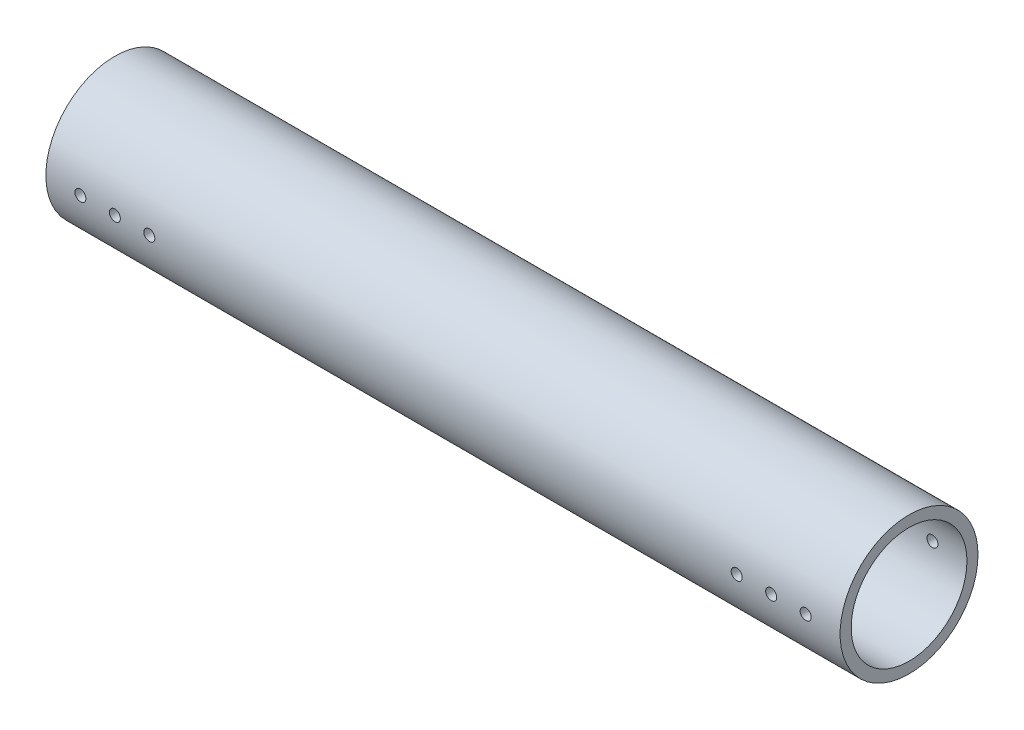
SolidWorks part; units mm, degrees
material "Zoltek Panex 33"
ref_plane "Спереди" through (0, 0, 0) normal (0, 0, 1) x (1, 0, 0)
ref_plane "Сверху" through (0, 0, 0) normal (0, 1, 0) x (1, 0, 0)
ref_plane "Справа" through (0, 0, 0) normal (1, 0, 0) x (0, 0, -1)
other "Configuration Table"
sketch "Эскиз2" plane through (0, 0, 0) normal (1, 0, 0) x (0, 0, -1)
  circle A0 centre (0, 0) radius 25
  circle A1 centre (0, 0) radius 21
  dimension "D1" = 50
  dimension "D2" = 42
extrude "Бобышка-Вытянуть2" add sketch "Эскиз2" along normal blind 288
ref_plane "Плоскость1" through (0, 0, 25) normal (0, 0, 1) x (1, 0, 0)
sketch "Эскиз4" plane through (0, 0, 25) normal (0, 0, 1) x (1, 0, 0)
  line L0 (0, -25) -> (288, -25) construction
  line L1 (288, -25) -> (288, 25) construction
  circle A0 centre (12.5, 0) radius 2
  circle A1 centre (275.5, 0) radius 2
  circle A2 centre (25, 0) radius 2
  circle A3 centre (37.5, 0) radius 2
  circle A4 centre (263, 0) radius 2
  circle A5 centre (250.5, 0) radius 2
  dimension "D1" = 4
  dimension "D4" = 4
  dimension "D6" = 4
  dimension "D8" = 4
  dimension "D10" = 4
  dimension "D11" = 4
  dimension "D2" = 12.5
  dimension "D3" = 25
  dimension "D5" = 12.5
  dimension "D7" = 12.5
  dimension "D9" = 12.5
  dimension "15" = 12.5
  dimension "D12" = 12.5
extrude "Вырез-Вытянуть2" cut sketch "Эскиз4" against normal through all and the other way blind 10 contours A0 | A1 | A2 | A3 | A5 | A4
equation "\"Diameter\"= 50мм"
equation "\"D1@Эскиз2\"= \"Diameter\""
equation "\"Length\"= 288мм"
equation "\"Thickness\"= 4мм"
equation "\"D1@Бобышка-Вытянуть2\"= \"Length\""
equation "\"D2@Эскиз2\" = \"Diameter\" - \"Thickness\" * 2"
equation "\"D4@Эскиз4\"=\"D1@Эскиз4\""
equation "\"D5@Эскиз4\"=\"D2@Эскиз4\""
equation "\"D3@Эскиз4\"=\"Diameter\"/2"
equation "\"D6@Эскиз4\"=\"D1@Эскиз4\""
equation "\"D8@Эскиз4\"=\"D6@Эскиз4\""
equation "\"D10@Эскиз4\"=\"D4@Эскиз4\""
equation "\"D11@Эскиз4\"=\"D4@Эскиз4\""
equation "\"D7@Эскиз4\"=\"D2@Эскиз4\""
equation "\"D9@Эскиз4\"=\"D2@Эскиз4\""
equation "\"D12@Эскиз4\"=\"D2@Эскиз4\""
equation "\"15@Эскиз4\"=\"D2@Эскиз4\""
